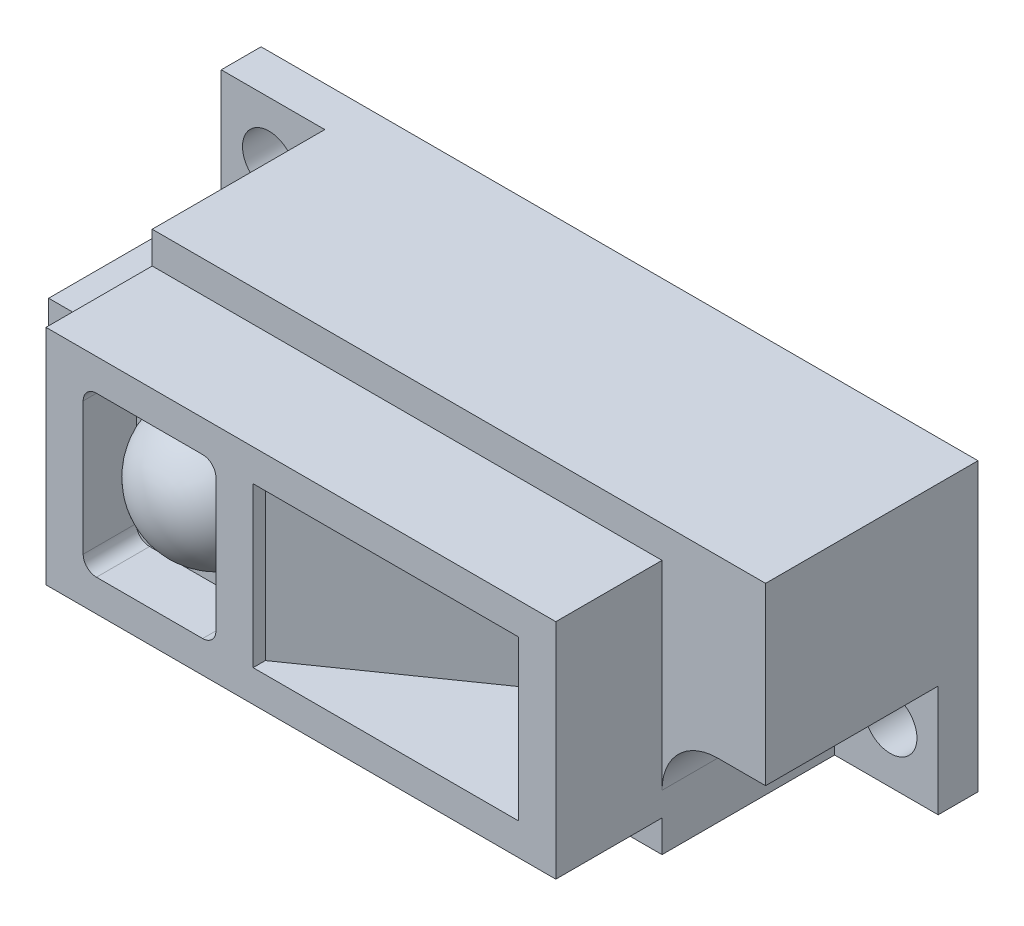
SolidWorks part; units mm, degrees
ref_plane "Front Plane" through (0, 0, 0) normal (0, 0, 1) x (1, 0, 0)
ref_plane "Top Plane" through (0, 0, 0) normal (0, 1, 0) x (1, 0, 0)
ref_plane "Right Plane" through (0, 0, 0) normal (1, 0, 0) x (0, 0, -1)
sketch "Sketch1" plane through (0, 0, 0) normal (0, 0, 1) x (1, 0, 0)
  line L1 (-13.5, -5.4) -> (13.5, -5.4)
  line L2 (-13.5, -5.4) -> (-13.5, 5.4)
  line L3 (-13.5, 5.4) -> (13.5, 5.4)
  line L4 (13.5, -5.4) -> (13.5, 5.4)
  line L5 (-13.5, -5.4) -> (13.5, 5.4) construction
  line L6 (-13.5, 5.4) -> (13.5, -5.4) construction
  point P0 (0, 0)
  dimension "D1" = 27
  dimension "D2" = 10.8
extrude "Boss-Extrude1" add sketch "Sketch1" along normal blind 8
sketch "Sketch2" plane through (0, 0, 8) normal (0, 0, 1) x (1, 0, 0)
  line L0 (13.5, 5.4) -> (-13.5, 5.4) construction
  line L1 (-13.5, -5.4) -> (13.5, -5.4) construction
  line L2 (0, -5.4) -> (0, 5.4) construction
  line L3 (11.7, -1.2) -> (13.5, -1.2)
  line L10 (13.5, -5.4) -> (13.5, 5.4) construction
  line L11 (9.6, -3.3) -> (9.6, -5.4)
  line L12 (9.6, -5.4) -> (13.5, -5.4)
  line L13 (13.5, -5.4) -> (13.5, -1.2)
  line L14 (-9.6, 3.3) -> (-9.6, 5.4)
  line L15 (-9.6, 5.4) -> (-13.5, 5.4)
  line L16 (-13.5, 5.4) -> (-13.5, 1.2)
  line L17 (-13.5, 5.4) -> (-13.5, -5.4) construction
  line L18 (-13.5, 1.2) -> (-11.7, 1.2)
  circle A0 centre (-11.7, 3.3) radius 1
  circle A1 centre (11.7, -3.3) radius 1
  arc A2 (9.6, -3.3) -> (11.7, -1.2) centre (11.7, -3.3) cw
  arc A3 (-9.6, 3.3) -> (-11.7, 1.2) centre (-11.7, 3.3) cw
  point P10 (0, 0)
  dimension "D1" = 2
  dimension "D2" = 2.1
  dimension "D3" = 23.4
  dimension "D4" = 2.1
  dimension "D5" = 11.7
extrude "Cut-Extrude3" cut sketch "Sketch2" against normal through all contours A0 | A1
extrude "Cut-Extrude4" cut sketch "Sketch2<3>" against normal blind 6.5
sketch "Sketch2<3>" plane through (0, 0, 8) normal (0, 0, 1) x (1, 0, 0) same geometry as "Sketch2"
sketch "Sketch6" plane through (0, -5.4, 0) normal (0, -1, 0) x (1, 0, 0)
  line L0 (-13.5, 0) -> (13.5, 0) construction
  line L1 (-13.5, 8) -> (-3.65, 8)
  line L2 (-13.5, 8) -> (-13.5, 0)
  line L3 (-13.5, 0) -> (-3.65, 0)
  line L4 (-3.65, 8) -> (-3.65, 0)
  dimension "D1" = 9.85
extrude "Cut-Extrude5" cut sketch "Sketch6" against normal blind 1.2
sketch "Sketch7" plane through (0, 0, 8) normal (0, 0, 1) x (1, 0, 0)
  line L0 (-3.65, -4.2) -> (-13.5, -4.2) construction
  line L1 (9.6, 4.2) -> (-9.6, 4.2)
  line L2 (9.6, 4.2) -> (9.6, -4.2)
  line L3 (9.6, -4.2) -> (-9.6, -4.2)
  line L4 (-9.6, 4.2) -> (-9.6, -4.2)
  line L5 (9.6, 4.2) -> (-9.6, -4.2) construction
  line L6 (9.6, -4.2) -> (-9.6, 4.2) construction
  line L7 (9.6, -3.3) -> (9.6, -5.4) construction
  point P0 (0, 0)
extrude "Boss-Extrude2" add sketch "Sketch7" along normal blind 4
sketch "Sketch9" plane through (0, 0, 12) normal (0, 0, 1) x (1, 0, 0)
  line L0 (-9.6, 3.3) -> (-9.6, -4.2) construction
  line L1 (-7.7, 3) -> (-3.7, 3)
  line L2 (-8.2, 2.5) -> (-8.2, -2.5)
  line L3 (-7.7, -3) -> (-3.7, -3)
  line L4 (-3.2, 2.5) -> (-3.2, -2.5)
  arc A0 (-3.7, 3) -> (-3.2, 2.5) centre (-3.7, 2.5) cw
  arc A1 (-3.7, -3) -> (-3.2, -2.5) centre (-3.7, -2.5) ccw
  arc A2 (-8.2, -2.5) -> (-7.7, -3) centre (-7.7, -2.5) ccw
  arc A3 (-7.7, 3) -> (-8.2, 2.5) centre (-7.7, 2.5) ccw
  point P4 (-3.2, 0)
  point P10 (-3.2, 3)
  point P15 (-8.2, -3)
  point P18 (-8.2, 3)
  dimension "D4" = 0.5
  dimension "D1" = 5
  dimension "D2" = 6
  dimension "D3" = 1.4
extrude "Cut-Extrude6" cut sketch "Sketch9" against normal blind 2
sketch "Sketch10" plane through (0, 0, 10) normal (0, 0, 1) x (1, 0, 0)
  line L2 (0, 0) -> (-8.2, 0) construction
  line L4 (-5.7, 3) -> (-5.7, -3) construction
  line L5 (-3.7, 3) -> (-7.7, 3) construction
  line L6 (-7.7, -3) -> (-3.7, -3) construction
  circle A1 centre (-5.7, 0) radius 2.45
  dimension "D1" = 4.9
extrude "Boss-Extrude5" add sketch "Sketch10" along normal blind 0.1 contours A1
dome "Dome1" faces to dome 1 distance 1.9 reverse direction no elliptical dome no face at (-3.25, 0, 10.1) parameters "D1"=1.9
sketch "Sketch11" plane through (0, 0, 12) normal (0, 0, 1) x (1, 0, 0)
  line L1 (-1.8, 3) -> (8.2, 3)
  line L2 (-1.8, 3) -> (-1.8, -3)
  line L3 (-1.8, -3) -> (8.2, -3)
  line L4 (8.2, 3) -> (8.2, -3)
  line L7 (9.6, 4.2) -> (-9.6, 4.2) construction
  line L8 (-3.2, -2.5) -> (-3.2, 2.5) construction
  line L9 (9.6, -4.2) -> (9.6, 4.2) construction
  dimension "D1" = 6
  dimension "D2" = 1.2
  dimension "D3" = 1.4
  dimension "D4" = 1.4
extrude "Cut-Extrude7" cut sketch "Sketch11" against normal blind 5
sketch "Sketch12" plane through (0, 0, 7) normal (0, 0, 1) x (1, 0, 0)
  circle A0 centre (6.5844, 0) radius 1.5
  dimension "D1" = 3
extrude "Cut-Extrude8" cut sketch "Sketch12" against normal blind 0.1
sketch "Sketch13" plane through (0, 3, 0) normal (0, -1, 0) x (1, 0, 0)
  line L0 (-1.8, 11.538) -> (4.7, 7)
  line L1 (-1.8, 7) -> (-1.8, 12) construction
  line L2 (8.2, 7) -> (-1.8, 7) construction
  line L3 (4.7, 7) -> (-1.8, 7)
  line L4 (-1.8, 7) -> (-1.8, 11.538)
  dimension "D1" = 3.5
extrude "Boss-Extrude6" add sketch "Sketch13" along normal up to next
dome "Dome2" faces to dome 1 distance 1.3 reverse direction no elliptical dome no face at (8.0844, 0, 6.9) parameters "D1"=1.3
sketch "Sketch14" plane through (0, -4.2, 0) normal (0, -1, 0) x (1, 0, 0)
  line L0 (-3.65, 0) -> (-3.65, 8) construction
  line L1 (-12.35, 2.5) -> (-3.65, 2.5)
  line L2 (-12.35, 2.5) -> (-12.35, 1.5)
  line L3 (-12.35, 1.5) -> (-3.65, 1.5)
  line L4 (-3.65, 2.5) -> (-3.65, 1.5)
  line L5 (-13.5, 0) -> (-3.65, 0) construction
  dimension "D1" = 8.7
  dimension "D2" = 1
  dimension "D3" = 2.5
extrude "Boss-Extrude7" add sketch "Sketch14" along normal blind 3.5 separate body
sketch "Sketch15" plane through (0, 0, 1.5) normal (0, 0, -1) x (-1, 0, 0)
  line L5 (8, -7.7) -> (8, -4.2) construction
  line L6 (12.35, -7.7) -> (3.65, -7.7) construction
  line L7 (13.5, -4.2) -> (3.65, -4.2) construction
  line L8 (11, -7.2) -> (5, -7.2)
  line L9 (11, -7.2) -> (11, -4.2)
  line L10 (11, -4.2) -> (5, -4.2)
  line L11 (5, -7.2) -> (5, -4.2)
  line L12 (11, -7.2) -> (5, -4.2) construction
  line L13 (11, -4.2) -> (5, -7.2) construction
  point P0 (8, -5.7)
  dimension "D1" = 6
  dimension "D2" = 3
extrude "Boss-Extrude9" add sketch "Sketch15" along normal blind 4 separate body
shell "Shell1" thickness 0.3 removed face at (-8, -5.7, -2.5)
